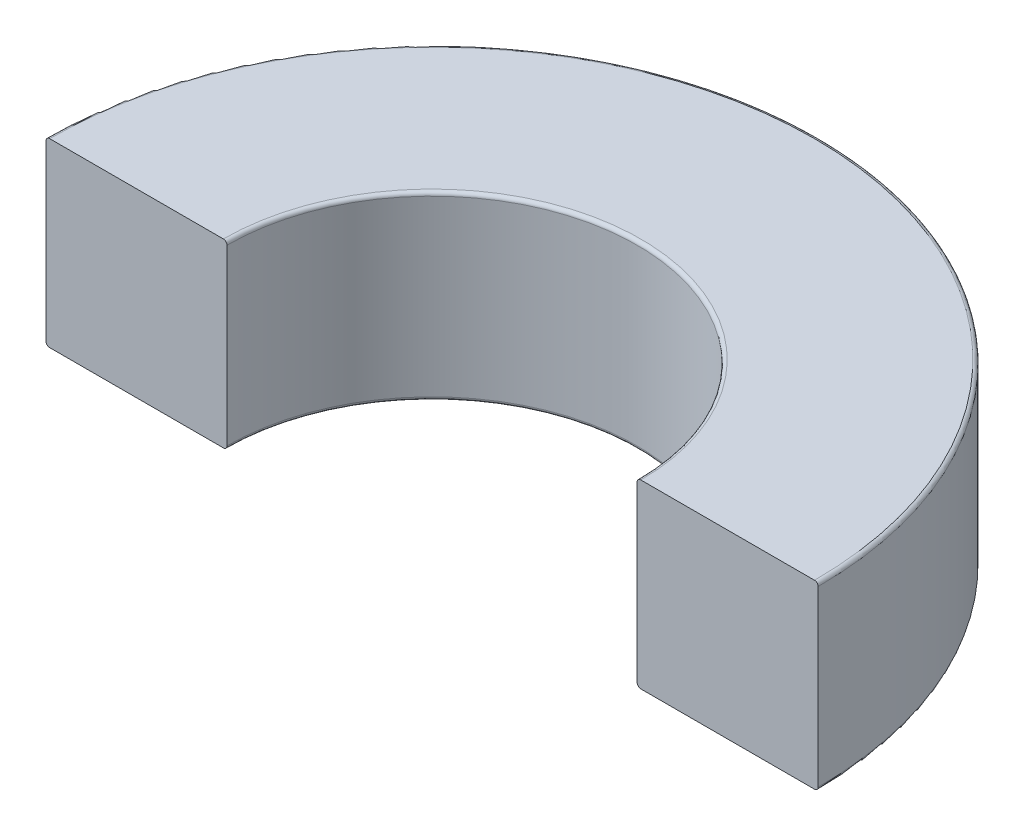
SolidWorks part; units mm, degrees
ref_plane "Front Plane" through (0, 0, 0) normal (0, 0, 1) x (1, 0, 0)
ref_plane "Top Plane" through (0, 0, 0) normal (0, 1, 0) x (1, 0, 0)
ref_plane "Right Plane" through (0, 0, 0) normal (1, 0, 0) x (0, 0, -1)
sketch "Sketch1" plane through (0, 0, 0) normal (0, 1, 0) x (1, 0, 0)
  line L0 (-566.6, 0) -> (-1066.6, 0)
  line L1 (566.6, 0) -> (1066.6, 0)
  arc A0 (-566.6, 0) -> (566.6, 0) centre (0, 0) cw
  arc A1 (-1066.6, 0) -> (1066.6, 0) centre (0, 0) cw
  point P6 (0, 0)
  dimension "D1" = 566.6
  dimension "D2" = 1066.6
extrude "Boss-Extrude1" add sketch "Sketch1" along normal blind 500
fillet "Fillet1" radius 10 4 edges at (0, 500, -1066.6) (0, 0, -1066.6) (0, 0, -566.6) (0, 500, -566.6)
